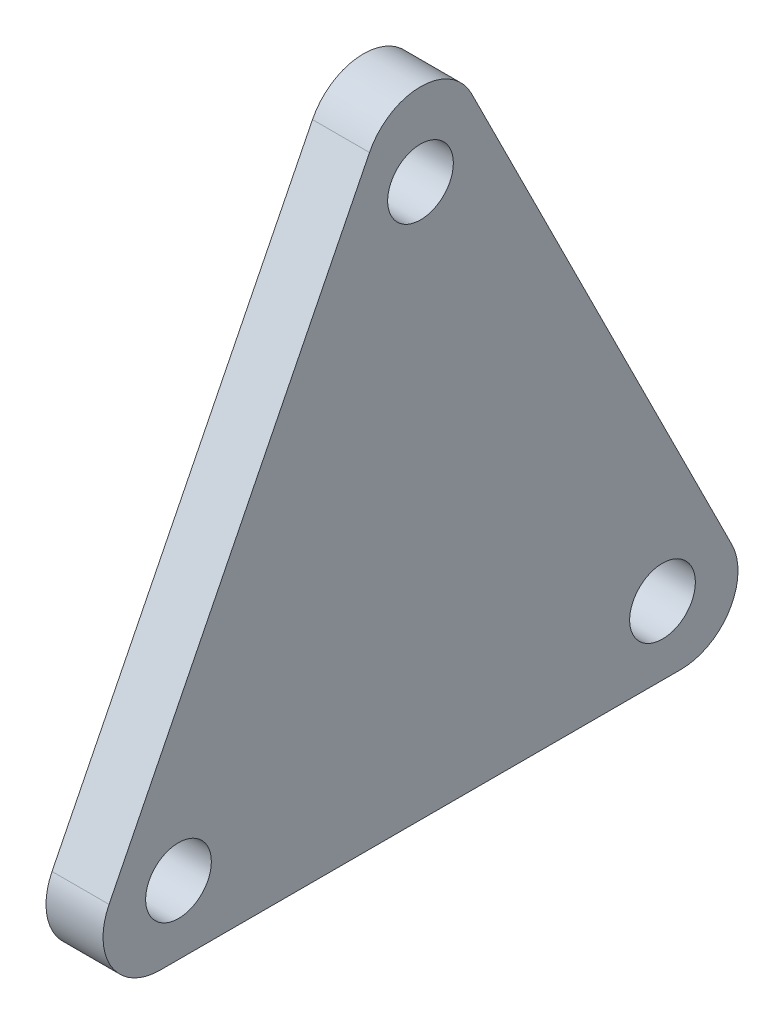
SolidWorks part; units mm, degrees
ref_plane "Front Plane" through (0, 0, 0) normal (0, 0, 1) x (1, 0, 0)
ref_plane "Top Plane" through (0, 0, 0) normal (0, 1, 0) x (1, 0, 0)
ref_plane "Right Plane" through (0, 0, 0) normal (1, 0, 0) x (0, 0, -1)
sketch "Sketch1" plane through (0, 0, 0) normal (1, 0, 0) x (0, 0, -1)
  line L0 (-13.4747, 0) -> (13.4747, 0) construction
  line L1 (0, 0) -> (0, 26.9494) construction
  line L2 (-13.4747, 0) -> (0, 26.9494) construction
  line L3 (0, 26.9494) -> (13.4747, 0) construction
  line L4 (13.4747, 0) -> (-13.4747, 0) construction
  line L5 (19.6394, -3.81) -> (-19.6394, -3.81)
  line L6 (-19.6394, -3.81) -> (0, 35.4688)
  line L7 (0, 35.4688) -> (19.6394, -3.81)
  circle A0 centre (-13.4747, 0) radius 1.8288
  circle A1 centre (0, 26.9494) radius 1.8288
  circle A2 centre (13.4747, 0) radius 1.8288
  point P4 (0, 0)
  dimension "D3" = 3.6576
  dimension "D1" = 26.9494
  dimension "D2" = 3.81
extrude "Boss-Extrude1" add sketch "Sketch1" along normal blind 3.175
fillet "Fillet1" radius 3.175 3 edges at (1.5875, 35.4688, 0) (1.5875, -3.81, -19.6394) (1.5875, -3.81, 19.6394)
